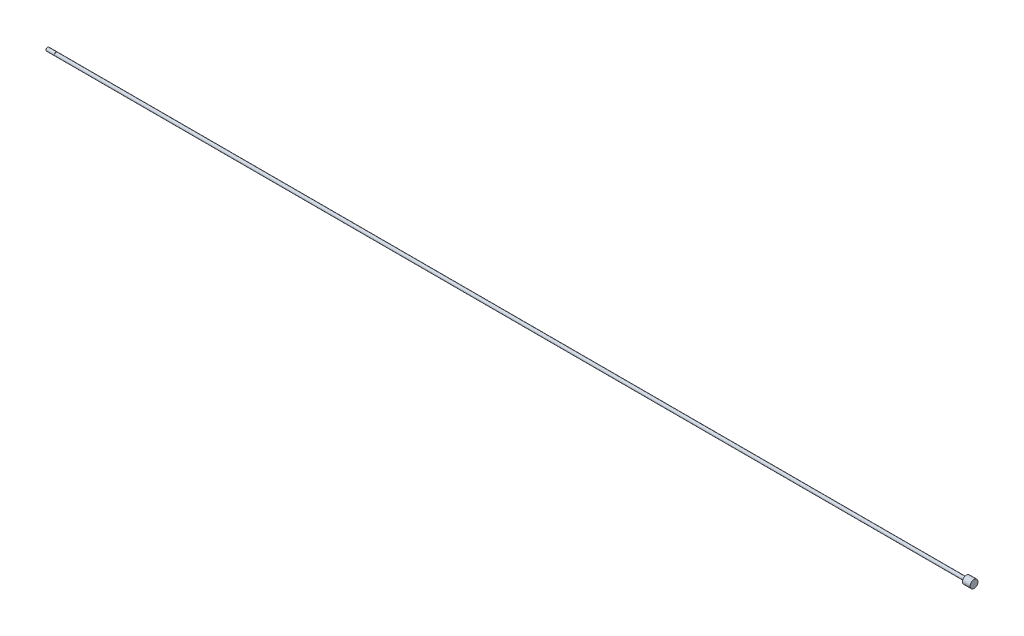
SolidWorks part; units mm, degrees
material "AISI 304"
ref_plane "Front Plane" through (0, 0, 0) normal (0, 0, 1) x (1, 0, 0)
ref_plane "Top Plane" through (0, 0, 0) normal (0, 1, 0) x (1, 0, 0)
ref_plane "Right Plane" through (0, 0, 0) normal (1, 0, 0) x (0, 0, -1)
sketch "Sketch1" plane through (0, 0, 0) normal (0, 0, 1) x (1, 0, 0)
  line L0 (0, 0) -> (0, 2.3749)
  line L1 (0, 2.3749) -> (1300.1752, 2.3749)
  line L2 (1300.1752, 2.3749) -> (1300.1752, 5.6197)
  line L3 (1300.1752, 5.6197) -> (1311.1988, 5.6197)
  line L4 (1311.1988, 5.6197) -> (1311.1988, 0)
  line L5 (1311.1988, 0) -> (0, 0)
  line L6 (1311.1988, 0) -> (0, 0) construction
revolve "Revolve1" add sketch "Sketch1" angle 360 about L6 reverse direction yes
sketch "Sketch2" plane through (0, 0, 0) normal (0, 0, 1) x (1, 0, 0)
  line L0 (-12.7, 0) -> (-12.7, 1.9406)
  line L1 (-12.7, 1.9406) -> (-12.2276, 2.413)
  line L2 (-12.2276, 2.413) -> (0, 2.413)
  line L3 (0, 2.413) -> (0, 0)
  line L4 (0, 0) -> (-12.7, 0)
  line L5 (0, 0) -> (-12.7, 0) construction
revolve "Revolve2" add sketch "Sketch2" angle 360 about L5 reverse direction yes
cosmetic thread "Cosmetic Thread1" parameters "D1"=12.7, "D2"=3.8811
ref_plane "Plane1" through (0, 0, 0) normal (1, 0, 0) x (0, 0, -1)
ref_plane "Plane2" through (0, 0, 0) normal (1, 0, 0) x (0, 0, -1)
ref_plane "Plane3" through (2611.374, 0, 0) normal (1, 0, 0) x (0, 0, -1)
ref_plane "Plane4" through (-12.7, 0, 0) normal (1, 0, 0) x (0, 0, -1)
sketch "Sketch3" plane through (0, 0, 0) normal (0, 0, 1) x (1, 0, 0)
  line L0 (-0.254, 2.667) -> (-0.254, 2.159)
  line L1 (-0.254, 2.159) -> (0, 2.159)
  line L2 (0, 2.159) -> (0, 2.667)
  line L3 (0, 2.667) -> (-0.254, 2.667)
  line L4 (0, 0) -> (-0.254, 0) construction
revolve "Cut-Revolve1" cut sketch "Sketch3" angle 360 about L4 reverse direction yes
ref_plane "Plane5" through (0, 0, 0) normal (1, 0, 0) x (0, 0, -1)
ref_plane "Plane6" through (-12.7, 0, 0) normal (1, 0, 0) x (0, 0, -1)
ref_plane "dia1 XY" through (0, 0, 0) normal (1, 0, 0) x (0, 0, -1)
ref_plane "dia1 XZ" through (0, 2.3749, 0) normal (0, -1, 0) x (-1, 0, 0)
ref_plane "dia1 YZ" through (0, 0, 0) normal (0, 0, -1) x (-1, 0, 0)
ref_axis "dia1 X" through (0, 2.3749, 80.9) along (0, 0, -1)
ref_axis "dia1 Y" through (0, -50, 0) along (0, 1, 0)
ref_axis "dia1 Z" through (80.9, 2.3749, 0) along (-1, 0, 0)
sketch3d "dia1"
  point P0 (0, 2.3749, 0)
ref_plane "dia12 XY" through (0, 0, 0) normal (1, 0, 0) x (0, 0, -1)
ref_plane "dia12 XZ" through (0, 0, 0) normal (0, -1, 0) x (-1, 0, 0)
ref_plane "dia12 YZ" through (0, 0, 9.3726) normal (0, 0, -1) x (-1, 0, 0)
ref_axis "dia12 X" through (0, 0, 80.9) along (0, 0, -1)
ref_axis "dia12 Y" through (0, -50, 9.3726) along (0, 1, 0)
ref_axis "dia12 Z" through (80.9, 0, 9.3726) along (-1, 0, 0)
sketch3d "dia12"
  point P0 (0, 0, 9.3726)
ref_plane "dia2 XY" through (0, 0, 0) normal (1, 0, 0) x (0, 0, -1)
ref_plane "dia2 XZ" through (0, -2.3749, 0) normal (0, -1, 0) x (-1, 0, 0)
ref_plane "dia2 YZ" through (0, 0, 0) normal (0, 0, -1) x (-1, 0, 0)
ref_axis "dia2 X" through (0, -2.3749, 80.9) along (0, 0, -1)
ref_axis "dia2 Y" through (0, -50, 0) along (0, 1, 0)
ref_axis "dia2 Z" through (80.9, -2.3749, 0) along (-1, 0, 0)
sketch3d "dia2"
  point P0 (0, -2.3749, 0)
ref_plane "dia22 XY" through (0, 0, 0) normal (1, 0, 0) x (0, 0, -1)
ref_plane "dia22 XZ" through (0, 0, 0) normal (0, -1, 0) x (-1, 0, 0)
ref_plane "dia22 YZ" through (0, 0, -9.3726) normal (0, 0, -1) x (-1, 0, 0)
ref_axis "dia22 X" through (0, 0, 80.9) along (0, 0, -1)
ref_axis "dia22 Y" through (0, -50, -9.3726) along (0, 1, 0)
ref_axis "dia22 Z" through (80.9, 0, -9.3726) along (-1, 0, 0)
sketch3d "dia22"
  point P0 (0, 0, -9.3726)
ref_plane "rl1 XY" through (-12.7, 0, 0) normal (1, 0, 0) x (0, 0, -1)
ref_plane "rl1 XZ" through (0, 0, 0) normal (0, -1, 0) x (-1, 0, 0)
ref_plane "rl1 YZ" through (0, 0, 0) normal (0, 0, -1) x (-1, 0, 0)
ref_axis "rl1 X" through (-12.7, 0, 80.9) along (0, 0, -1)
ref_axis "rl1 Y" through (-12.7, -50, 0) along (0, 1, 0)
ref_axis "rl1 Z" through (80.9, 0, 0) along (-1, 0, 0)
sketch3d "rl1"
  point P0 (-12.7, 0, 0)
ref_plane "rl2 XY" through (0, 0, 0) normal (1, 0, 0) x (0, 0, -1)
ref_plane "rl2 XZ" through (0, 0, 0) normal (0, -1, 0) x (-1, 0, 0)
ref_plane "rl2 YZ" through (0, 0, 0) normal (0, 0, -1) x (-1, 0, 0)
ref_axis "rl2 X" through (0, 0, 80.9) along (0, 0, -1)
ref_axis "rl2 Y" through (0, -50, 0) along (0, 1, 0)
ref_axis "rl2 Z" through (80.9, 0, 0) along (-1, 0, 0)
sketch3d "rl2"
  point P0 (0, 0, 0)
ref_plane "rod_cp XY" through (0, 0, 0) normal (1, 0, 0) x (0, 0, -1)
ref_plane "rod_cp XZ" through (0, 0, 0) normal (0, -1, 0) x (-1, 0, 0)
ref_plane "rod_cp YZ" through (0, 0, 0) normal (0, 0, -1) x (-1, 0, 0)
ref_axis "rod_cp X" through (0, 0, 80.9) along (0, 0, -1)
ref_axis "rod_cp Y" through (0, -50, 0) along (0, 1, 0)
ref_axis "rod_cp Z" through (80.9, 0, 0) along (-1, 0, 0)
sketch3d "rod_cp"
  point P0 (0, 0, 0)
ref_plane "thd1 XY" through (-12.7, 0, 0) normal (1, 0, 0) x (0, 0, -1)
ref_plane "thd1 XZ" through (0, 2.413, 0) normal (0, -1, 0) x (-1, 0, 0)
ref_plane "thd1 YZ" through (0, 0, 0) normal (0, 0, -1) x (-1, 0, 0)
ref_axis "thd1 X" through (-12.7, 2.413, 80.9) along (0, 0, -1)
ref_axis "thd1 Y" through (-12.7, -50, 0) along (0, 1, 0)
ref_axis "thd1 Z" through (80.9, 2.413, 0) along (-1, 0, 0)
sketch3d "thd1"
  point P0 (-12.7, 2.413, 0)
ref_plane "thd2 XY" through (-12.7, 0, 0) normal (1, 0, 0) x (0, 0, -1)
ref_plane "thd2 XZ" through (0, -2.413, 0) normal (0, -1, 0) x (-1, 0, 0)
ref_plane "thd2 YZ" through (0, 0, 0) normal (0, 0, -1) x (-1, 0, 0)
ref_axis "thd2 X" through (-12.7, -2.413, 80.9) along (0, 0, -1)
ref_axis "thd2 Y" through (-12.7, -50, 0) along (0, 1, 0)
ref_axis "thd2 Z" through (80.9, -2.413, 0) along (-1, 0, 0)
sketch3d "thd2"
  point P0 (-12.7, -2.413, 0)
ref_plane "to_rod_clevis XY" through (-12.7, 0, 0) normal (1, 0, 0) x (0, 0, -1)
ref_plane "to_rod_clevis XZ" through (0, 0, 0) normal (0, -1, 0) x (-1, 0, 0)
ref_plane "to_rod_clevis YZ" through (0, 0, 0) normal (0, 0, -1) x (-1, 0, 0)
ref_axis "to_rod_clevis X" through (-12.7, 0, 80.9) along (0, 0, -1)
ref_axis "to_rod_clevis Y" through (-12.7, -50, 0) along (0, 1, 0)
ref_axis "to_rod_clevis Z" through (80.9, 0, 0) along (-1, 0, 0)
sketch3d "to_rod_clevis"
  point P0 (-12.7, 0, 0)
